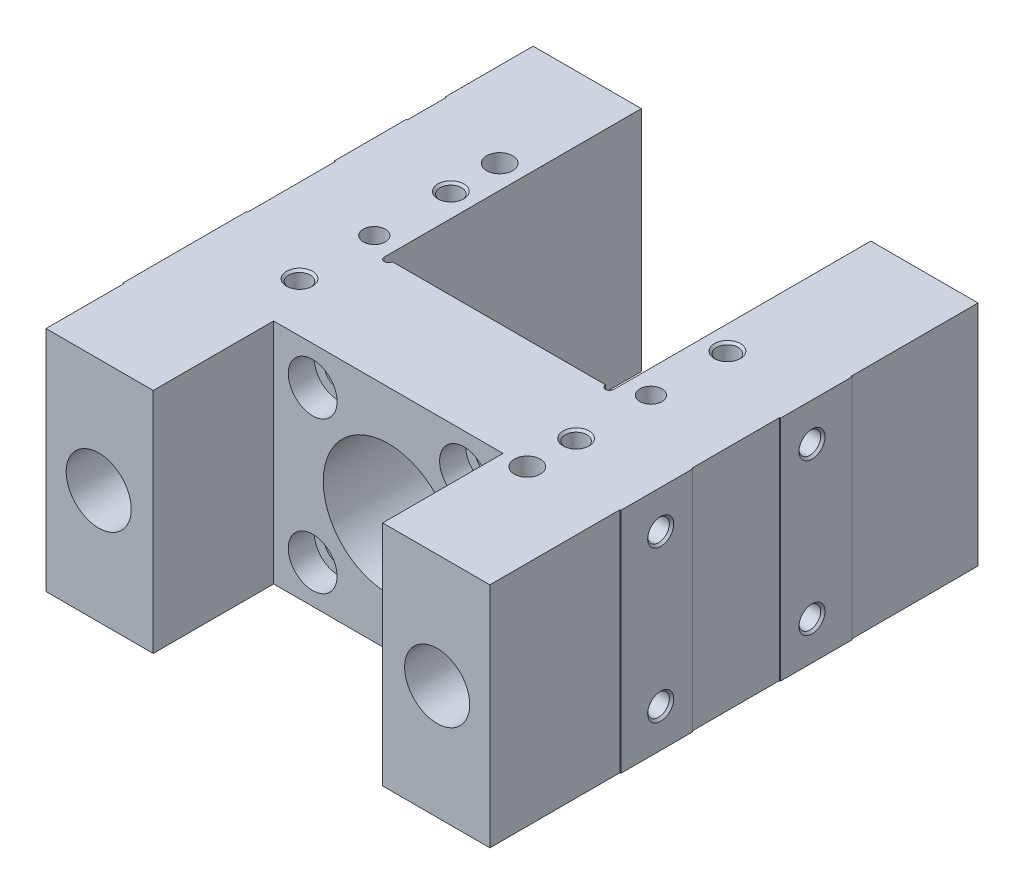
SolidWorks part; units mm, degrees
ref_plane "Front Plane" through (0, 0, 0) normal (0, 0, 1) x (1, 0, 0)
ref_plane "Top Plane" through (0, 0, 0) normal (0, 1, 0) x (1, 0, 0)
ref_plane "Right Plane" through (0, 0, 0) normal (1, 0, 0) x (0, 0, -1)
sketch "Sketch1" plane through (0, 0, 0) normal (0, 1, 0) x (1, 0, 0)
  line L0 (-68.5, -71) -> (-35.25, -71)
  line L1 (-35.25, -71) -> (-35.25, -34)
  line L2 (-35.25, -34) -> (35.25, -34)
  line L3 (35.25, -34) -> (35.25, -71)
  line L4 (35.25, -71) -> (68.5, -71)
  line L5 (68.5, -71) -> (68.5, 79)
  line L6 (68.5, 79) -> (35.25, 79)
  line L7 (35.25, 79) -> (35.25, 0)
  line L8 (32.75, 0) -> (-32.75, 0)
  line L9 (-35.25, 0) -> (-35.25, 79)
  line L10 (-35.25, 79) -> (-68.5, 79)
  line L11 (-68.5, 79) -> (-68.5, -71)
  arc A0 (35.25, 0) -> (32.75, 0) centre (34, 0) cw
  arc A1 (-32.75, 0) -> (-35.25, 0) centre (-34, 0) cw
extrude "Boss-Extrude1" add sketch "Sketch1" against normal blind 35 and the other way blind 35
sketch "Sketch2" plane through (0, 0, 0) normal (1, 0, 0) x (0, 0, -1)
  line L0 (-35, 0) -> (-35, 20)
  line L1 (-35, 20) -> (1, 20)
  line L2 (1, 20) -> (1, 0)
  line L3 (1, 0) -> (-35, 0)
  line L4 (1, 0) -> (-35, 0) construction
revolve "Cut-Revolve1" cut sketch "Sketch2" angle 360 about L4 reverse direction yes
ref_plane "Plane1" through (-23.25, 0, 0) normal (1, 0, 0) x (0, 0, -1)
sketch "Sketch3" plane through (-23.25, 0, 0) normal (1, 0, 0) x (0, 0, -1)
  line L0 (-34, 23.25) -> (-34, 30.75)
  line L1 (-34, 30.75) -> (-26, 30.75)
  line L2 (-26, 30.75) -> (-26, 27.75)
  line L3 (-26, 27.75) -> (0, 27.75)
  line L4 (0, 27.75) -> (0, 23.25)
  line L5 (0, 23.25) -> (-34, 23.25)
  line L6 (0, 23.25) -> (-34, 23.25) construction
revolve "Cut-Revolve2" cut sketch "Sketch3" angle 360 about L6 reverse direction yes
sketch "Sketch4" plane through (-23.25, 0, 0) normal (1, 0, 0) x (0, 0, -1)
  line L0 (-34, -23.25) -> (-34, -15.75)
  line L1 (-34, -15.75) -> (-26, -15.75)
  line L2 (-26, -15.75) -> (-26, -18.75)
  line L3 (-26, -18.75) -> (0, -18.75)
  line L4 (0, -18.75) -> (0, -23.25)
  line L5 (0, -23.25) -> (-34, -23.25)
  line L6 (0, -23.25) -> (-34, -23.25) construction
revolve "Cut-Revolve3" cut sketch "Sketch4" angle 360 about L6 reverse direction yes
ref_plane "Plane2" through (23.25, 0, 0) normal (1, 0, 0) x (0, 0, -1)
sketch "Sketch5" plane through (23.25, 0, 0) normal (1, 0, 0) x (0, 0, -1)
  line L0 (-34, 23.25) -> (-34, 30.75)
  line L1 (-34, 30.75) -> (-26, 30.75)
  line L2 (-26, 30.75) -> (-26, 27.75)
  line L3 (-26, 27.75) -> (0, 27.75)
  line L4 (0, 27.75) -> (0, 23.25)
  line L5 (0, 23.25) -> (-34, 23.25)
  line L6 (0, 23.25) -> (-34, 23.25) construction
revolve "Cut-Revolve4" cut sketch "Sketch5" angle 360 about L6 reverse direction yes
sketch "Sketch6" plane through (23.25, 0, 0) normal (1, 0, 0) x (0, 0, -1)
  line L0 (-34, -23.25) -> (-34, -15.75)
  line L1 (-34, -15.75) -> (-26, -15.75)
  line L2 (-26, -15.75) -> (-26, -18.75)
  line L3 (-26, -18.75) -> (0, -18.75)
  line L4 (0, -18.75) -> (0, -23.25)
  line L5 (0, -23.25) -> (-34, -23.25)
  line L6 (0, -23.25) -> (-34, -23.25) construction
revolve "Cut-Revolve5" cut sketch "Sketch6" angle 360 about L6 reverse direction yes
ref_plane "Plane3" through (0, 0, 18.8) normal (0, 0, 1) x (1, 0, 0)
hole_wizard "Hole1" positions "Sketch8" profile "Sketch7" legacy
sketch "Sketch8" plane through (0, 35, 0) normal (0, 1, 0) x (1, 0, 0)
  point P0 (42.5, -18.8)
sketch "Sketch7" plane through (42.5, 35, 18.8) normal (1, 0, 0) x (0, 0, 1)
  line L0 (0, 0) -> (0, 21.3333)
  line L1 (0, 21.3333) -> (3.3235, 19.4145)
  line L2 (3.3235, 19.4145) -> (3.3235, 0.6765)
  line L3 (3.3235, 0.6765) -> (4, 0)
  line L4 (4, 0) -> (0, 0)
  line L5 (0, -14.3089) -> (0, 102.4216) construction
  line L6 (0, 21.3333) -> (-3.3235, 19.4145) construction
  line L7 (-3.3235, 0.6765) -> (-4, 0) construction
  dimension "Diameter" = 6.647
  dimension "Depth" = 19.4145
  dimension "C-Sink Diameter" = 8
  dimension "C-Sink Angle" = 90
  dimension "Drill Angle" = 120
cosmetic thread "Cosmetic Thread1" parameters "D1"=16, "D2"=8
hole_wizard "Hole2" positions "Sketch10" profile "Sketch9" legacy
sketch "Sketch10" plane through (0, 35, 0) normal (0, 1, 0) x (1, 0, 0)
  point P0 (-42.5, -18.8)
sketch "Sketch9" plane through (-42.5, 35, 18.8) normal (1, 0, 0) x (0, 0, 1)
  line L0 (0, 0) -> (0, 21.3333)
  line L1 (0, 21.3333) -> (3.3235, 19.4145)
  line L2 (3.3235, 19.4145) -> (3.3235, 0.6765)
  line L3 (3.3235, 0.6765) -> (4, 0)
  line L4 (4, 0) -> (0, 0)
  line L5 (0, -14.3089) -> (0, 102.4216) construction
  line L6 (0, 21.3333) -> (-3.3235, 19.4145) construction
  line L7 (-3.3235, 0.6765) -> (-4, 0) construction
  dimension "Diameter" = 6.647
  dimension "Depth" = 19.4145
  dimension "C-Sink Diameter" = 8
  dimension "C-Sink Angle" = 90
  dimension "Drill Angle" = 120
cosmetic thread "Cosmetic Thread2" parameters "D1"=16, "D2"=8
sketch "Sketch11" plane through (0, 0, 18.8) normal (0, 0, 1) x (1, 0, 0)
  line L0 (48.5, 23.25) -> (50.4188, 26.5735)
  line L1 (50.4188, 26.5735) -> (67.8235, 26.5735)
  line L2 (67.8235, 26.5735) -> (68.5, 27.25)
  line L3 (68.5, 27.25) -> (68.5, 23.25)
  line L4 (68.5, 23.25) -> (48.5, 23.25)
  line L5 (68.5, 23.25) -> (48.5, 23.25) construction
revolve "Cut-Revolve6" cut sketch "Sketch11" angle 360 about L5
cosmetic thread "Cosmetic Thread3" parameters "D1"=16, "D2"=8
sketch "Sketch12" plane through (0, 0, 18.8) normal (0, 0, 1) x (1, 0, 0)
  line L0 (48.5, -23.25) -> (50.4188, -19.9265)
  line L1 (50.4188, -19.9265) -> (67.8235, -19.9265)
  line L2 (67.8235, -19.9265) -> (68.5, -19.25)
  line L3 (68.5, -19.25) -> (68.5, -23.25)
  line L4 (68.5, -23.25) -> (48.5, -23.25)
  line L5 (68.5, -23.25) -> (48.5, -23.25) construction
revolve "Cut-Revolve7" cut sketch "Sketch12" angle 360 about L5
cosmetic thread "Cosmetic Thread4" parameters "D1"=16, "D2"=8
sketch "Sketch13" plane through (0, 0, 18.8) normal (0, 0, 1) x (1, 0, 0)
  line L0 (-68.5, 23.25) -> (-68.5, 27.25)
  line L1 (-68.5, 27.25) -> (-67.8235, 26.5735)
  line L2 (-67.8235, 26.5735) -> (-50.4188, 26.5735)
  line L3 (-50.4188, 26.5735) -> (-48.5, 23.25)
  line L4 (-48.5, 23.25) -> (-68.5, 23.25)
  line L5 (-48.5, 23.25) -> (-68.5, 23.25) construction
revolve "Cut-Revolve8" cut sketch "Sketch13" angle 360 about L5
cosmetic thread "Cosmetic Thread5" parameters "D1"=16, "D2"=8
sketch "Sketch14" plane through (0, 0, 18.8) normal (0, 0, 1) x (1, 0, 0)
  line L0 (-68.5, -23.25) -> (-68.5, -19.25)
  line L1 (-68.5, -19.25) -> (-67.8235, -19.9265)
  line L2 (-67.8235, -19.9265) -> (-50.4188, -19.9265)
  line L3 (-50.4188, -19.9265) -> (-48.5, -23.25)
  line L4 (-48.5, -23.25) -> (-68.5, -23.25)
  line L5 (-48.5, -23.25) -> (-68.5, -23.25) construction
revolve "Cut-Revolve9" cut sketch "Sketch14" angle 360 about L5 reverse direction yes
cosmetic thread "Cosmetic Thread6" parameters "D1"=16, "D2"=8
ref_plane "Plane4" through (0, 0, -27.7) normal (0, 0, 1) x (1, 0, 0)
hole_wizard "Hole3" positions "Sketch16" profile "Sketch15" legacy
sketch "Sketch16" plane through (0, 35, 0) normal (0, 1, 0) x (1, 0, 0)
  point P0 (42.5, 27.7)
sketch "Sketch15" plane through (42.5, 35, -27.7) normal (1, 0, 0) x (0, 0, 1)
  line L0 (0, 0) -> (0, 21.3333)
  line L1 (0, 21.3333) -> (3.3235, 19.4145)
  line L2 (3.3235, 19.4145) -> (3.3235, 0.6765)
  line L3 (3.3235, 0.6765) -> (4, 0)
  line L4 (4, 0) -> (0, 0)
  line L5 (0, -14.3089) -> (0, 102.4216) construction
  line L6 (0, 21.3333) -> (-3.3235, 19.4145) construction
  line L7 (-3.3235, 0.6765) -> (-4, 0) construction
  dimension "Diameter" = 6.647
  dimension "Depth" = 19.4145
  dimension "C-Sink Diameter" = 8
  dimension "C-Sink Angle" = 90
  dimension "Drill Angle" = 120
cosmetic thread "Cosmetic Thread7" parameters "D1"=16, "D2"=8
sketch "Sketch17" plane through (0, 0, -27.7) normal (0, 0, 1) x (1, 0, 0)
  line L0 (-42.5, 35) -> (-38.5, 35)
  line L1 (-38.5, 35) -> (-39.1765, 34.3235)
  line L2 (-39.1765, 34.3235) -> (-39.1765, 15.5855)
  line L3 (-39.1765, 15.5855) -> (-42.5, 13.6667)
  line L4 (-42.5, 13.6667) -> (-42.5, 35)
  line L5 (-42.5, 13.6667) -> (-42.5, 35) construction
revolve "Cut-Revolve10" cut sketch "Sketch17" angle 360 about L5
cosmetic thread "Cosmetic Thread8" parameters "D1"=16, "D2"=8
sketch "Sketch18" plane through (0, 0, -27.7) normal (0, 0, 1) x (1, 0, 0)
  line L0 (48.5, 23.25) -> (50.4188, 26.5735)
  line L1 (50.4188, 26.5735) -> (67.8235, 26.5735)
  line L2 (67.8235, 26.5735) -> (68.5, 27.25)
  line L3 (68.5, 27.25) -> (68.5, 23.25)
  line L4 (68.5, 23.25) -> (48.5, 23.25)
  line L5 (68.5, 23.25) -> (48.5, 23.25) construction
revolve "Cut-Revolve11" cut sketch "Sketch18" angle 360 about L5
cosmetic thread "Cosmetic Thread9" parameters "D1"=16, "D2"=8
sketch "Sketch19" plane through (0, 0, -27.7) normal (0, 0, 1) x (1, 0, 0)
  line L0 (48.5, -23.25) -> (50.4188, -19.9265)
  line L1 (50.4188, -19.9265) -> (67.8235, -19.9265)
  line L2 (67.8235, -19.9265) -> (68.5, -19.25)
  line L3 (68.5, -19.25) -> (68.5, -23.25)
  line L4 (68.5, -23.25) -> (48.5, -23.25)
  line L5 (68.5, -23.25) -> (48.5, -23.25) construction
revolve "Cut-Revolve12" cut sketch "Sketch19" angle 360 about L5
cosmetic thread "Cosmetic Thread10" parameters "D1"=16, "D2"=8
sketch "Sketch20" plane through (0, 0, -27.7) normal (0, 0, 1) x (1, 0, 0)
  line L0 (-68.5, 23.25) -> (-68.5, 27.25)
  line L1 (-68.5, 27.25) -> (-67.8235, 26.5735)
  line L2 (-67.8235, 26.5735) -> (-50.4188, 26.5735)
  line L3 (-50.4188, 26.5735) -> (-48.5, 23.25)
  line L4 (-48.5, 23.25) -> (-68.5, 23.25)
  line L5 (-48.5, 23.25) -> (-68.5, 23.25) construction
revolve "Cut-Revolve13" cut sketch "Sketch20" angle 360 about L5
cosmetic thread "Cosmetic Thread11" parameters "D1"=16, "D2"=8
sketch "Sketch21" plane through (0, 0, -27.7) normal (0, 0, 1) x (1, 0, 0)
  line L0 (-68.5, -23.25) -> (-68.5, -19.25)
  line L1 (-68.5, -19.25) -> (-67.8235, -19.9265)
  line L2 (-67.8235, -19.9265) -> (-50.4188, -19.9265)
  line L3 (-50.4188, -19.9265) -> (-48.5, -23.25)
  line L4 (-48.5, -23.25) -> (-68.5, -23.25)
  line L5 (-48.5, -23.25) -> (-68.5, -23.25) construction
revolve "Cut-Revolve14" cut sketch "Sketch21" angle 360 about L5
cosmetic thread "Cosmetic Thread12" parameters "D1"=16, "D2"=8
ref_plane "Plane5" through (0, 0, -63) normal (0, 0, 1) x (1, 0, 0)
sketch "Sketch22" plane through (0, 0, -63) normal (0, 0, 1) x (1, 0, 0)
  line L0 (-68.5, 23.25) -> (-68.5, 27.25)
  line L1 (-68.5, 27.25) -> (-67.8235, 26.5735)
  line L2 (-67.8235, 26.5735) -> (-50.4188, 26.5735)
  line L3 (-50.4188, 26.5735) -> (-48.5, 23.25)
  line L4 (-48.5, 23.25) -> (-68.5, 23.25)
  line L5 (-48.5, 23.25) -> (-68.5, 23.25) construction
revolve "Cut-Revolve15" cut sketch "Sketch22" angle 360 about L5
cosmetic thread "Cosmetic Thread13" parameters "D1"=16, "D2"=8
sketch "Sketch23" plane through (0, 0, -63) normal (0, 0, 1) x (1, 0, 0)
  line L0 (-68.5, -23.25) -> (-68.5, -19.25)
  line L1 (-68.5, -19.25) -> (-67.8235, -19.9265)
  line L2 (-67.8235, -19.9265) -> (-50.4188, -19.9265)
  line L3 (-50.4188, -19.9265) -> (-48.5, -23.25)
  line L4 (-48.5, -23.25) -> (-68.5, -23.25)
  line L5 (-48.5, -23.25) -> (-68.5, -23.25) construction
revolve "Cut-Revolve16" cut sketch "Sketch23" angle 360 about L5
cosmetic thread "Cosmetic Thread14" parameters "D1"=16, "D2"=8
ref_plane "Plane6" through (0, 0, 37) normal (0, 0, 1) x (1, 0, 0)
sketch "Sketch24" plane through (0, 0, 37) normal (0, 0, 1) x (1, 0, 0)
  line L0 (-68.5, 23.25) -> (-68.5, 27.25)
  line L1 (-68.5, 27.25) -> (-67.8235, 26.5735)
  line L2 (-67.8235, 26.5735) -> (-50.4188, 26.5735)
  line L3 (-50.4188, 26.5735) -> (-48.5, 23.25)
  line L4 (-48.5, 23.25) -> (-68.5, 23.25)
  line L5 (-48.5, 23.25) -> (-68.5, 23.25) construction
revolve "Cut-Revolve17" cut sketch "Sketch24" angle 360 about L5
cosmetic thread "Cosmetic Thread15" parameters "D1"=16, "D2"=8
sketch "Sketch25" plane through (0, 0, 37) normal (0, 0, 1) x (1, 0, 0)
  line L0 (-68.5, -23.25) -> (-68.5, -19.25)
  line L1 (-68.5, -19.25) -> (-67.8235, -19.9265)
  line L2 (-67.8235, -19.9265) -> (-50.4188, -19.9265)
  line L3 (-50.4188, -19.9265) -> (-48.5, -23.25)
  line L4 (-48.5, -23.25) -> (-68.5, -23.25)
  line L5 (-48.5, -23.25) -> (-68.5, -23.25) construction
revolve "Cut-Revolve18" cut sketch "Sketch25" angle 360 about L5
cosmetic thread "Cosmetic Thread16" parameters "D1"=16, "D2"=8
ref_plane "Plane7" through (0, 0, -79) normal (0, 0, 1) x (1, 0, 0)
sketch "Sketch26" plane through (0, 0, -79) normal (0, 0, 1) x (1, 0, 0)
  circle A0 centre (52, 0) radius 10
extrude "Cut-Extrude1" cut sketch "Sketch26" along normal blind 150
sketch "Sketch27" plane through (0, 0, -79) normal (0, 0, 1) x (1, 0, 0)
  circle A0 centre (-52, 0) radius 10
extrude "Cut-Extrude2" cut sketch "Sketch27" along normal blind 150
ref_plane "Plane8" through (0, 0, 26) normal (0, 0, 1) x (1, 0, 0)
ref_plane "Plane9" through (0, 0, 0) normal (0, 0, 1) x (1, 0, 0)
sketch "Sketch28" plane through (0, 0, 0) normal (0, 1, 0) x (1, 0, 0)
  line L0 (-88.5, -91) -> (88.5, -91)
  line L1 (88.5, -91) -> (88.5, 99)
  line L2 (88.5, 99) -> (-88.5, 99)
  line L3 (-88.5, 99) -> (-88.5, -91)
  line L4 (-68.5, 18) -> (-68.2, 18)
  line L5 (-68.2, 18) -> (-68.2, -9)
  line L6 (-68.2, -9) -> (-68.5, -9)
  line L7 (-68.5, -9) -> (-68.5, -47)
  line L8 (-68.5, -47) -> (-68.2, -47)
  line L9 (-68.2, -47) -> (-68.2, -71)
  line L10 (-68.2, -71) -> (68.2, -71)
  line L11 (68.2, -71) -> (68.2, -31)
  line L12 (68.2, -31) -> (68.5, -31)
  line L13 (68.5, -31) -> (68.5, -9)
  line L14 (68.5, -9) -> (68.2, -9)
  line L15 (68.2, -9) -> (68.2, 18)
  line L16 (68.2, 18) -> (68.5, 18)
  line L17 (68.5, 18) -> (68.5, 40)
  line L18 (68.5, 40) -> (68.2, 40)
  line L19 (68.2, 40) -> (68.2, 79)
  line L20 (68.2, 79) -> (-68.5, 79)
  line L21 (-68.5, 79) -> (-68.5, 52)
  line L22 (-68.5, 52) -> (-68.2, 52)
  line L23 (-68.2, 52) -> (-68.2, 40)
  line L24 (-68.2, 40) -> (-68.5, 40)
  line L25 (-68.5, 40) -> (-68.5, 18)
extrude "Cut-Extrude3" cut sketch "Sketch28" along normal blind 70 and the other way blind 70
ref_plane "Plane10" through (0, 0, 18.8) normal (0, 0, 1) x (1, 0, 0)
ref_plane "Plane11" through (-68.2, 0, 0) normal (1, 0, 0) x (0, 0, -1)
ref_plane "Plane12" through (0, 35, 0) normal (0, 1, 0) x (1, 0, 0)
ref_plane "DIN912 1 XY" through (0, 0, 26) normal (0, 0, 1) x (1, 0, 0)
ref_plane "DIN912 1 XZ" through (0, 23.25, 0) normal (0, -1, 0) x (-1, 0, 0)
ref_plane "DIN912 1 YZ" through (23.25, 0, 0) normal (1, 0, 0) x (0, 0, -1)
ref_axis "DIN912 1 X" through (-80.9, 23.25, 26) along (1, 0, 0)
ref_axis "DIN912 1 Y" through (23.25, -50, 26) along (0, 1, 0)
ref_axis "DIN912 1 Z" through (23.25, 23.25, 80.9) along (0, 0, -1)
sketch3d "DIN912 1"
  point P0 (23.25, 23.25, 26)
ref_plane "DIN912 2 XY" through (0, 0, 26) normal (0, 0, 1) x (1, 0, 0)
ref_plane "DIN912 2 XZ" through (0, 23.25, 0) normal (0, -1, 0) x (-1, 0, 0)
ref_plane "DIN912 2 YZ" through (-23.25, 0, 0) normal (1, 0, 0) x (0, 0, -1)
ref_axis "DIN912 2 X" through (-80.9, 23.25, 26) along (1, 0, 0)
ref_axis "DIN912 2 Y" through (-23.25, -50, 26) along (0, 1, 0)
ref_axis "DIN912 2 Z" through (-23.25, 23.25, 80.9) along (0, 0, -1)
sketch3d "DIN912 2"
  point P0 (-23.25, 23.25, 26)
ref_plane "DIN912 3 XY" through (0, 0, 26) normal (0, 0, 1) x (1, 0, 0)
ref_plane "DIN912 3 XZ" through (0, -23.25, 0) normal (0, -1, 0) x (-1, 0, 0)
ref_plane "DIN912 3 YZ" through (23.25, 0, 0) normal (1, 0, 0) x (0, 0, -1)
ref_axis "DIN912 3 X" through (-80.9, -23.25, 26) along (1, 0, 0)
ref_axis "DIN912 3 Y" through (23.25, -50, 26) along (0, 1, 0)
ref_axis "DIN912 3 Z" through (23.25, -23.25, 80.9) along (0, 0, -1)
sketch3d "DIN912 3"
  point P0 (23.25, -23.25, 26)
ref_plane "DIN912 4 XY" through (0, 0, 26) normal (0, 0, 1) x (1, 0, 0)
ref_plane "DIN912 4 XZ" through (0, -23.25, 0) normal (0, -1, 0) x (-1, 0, 0)
ref_plane "DIN912 4 YZ" through (-23.25, 0, 0) normal (1, 0, 0) x (0, 0, -1)
ref_axis "DIN912 4 X" through (-80.9, -23.25, 26) along (1, 0, 0)
ref_axis "DIN912 4 Y" through (-23.25, -50, 26) along (0, 1, 0)
ref_axis "DIN912 4 Z" through (-23.25, -23.25, 80.9) along (0, 0, -1)
sketch3d "DIN912 4"
  point P0 (-23.25, -23.25, 26)
ref_plane "JOCH XY" through (0, 0, 0) normal (0, 0, 1) x (1, 0, 0)
ref_plane "JOCH XZ" through (0, 0, 0) normal (0, -1, 0) x (-1, 0, 0)
ref_plane "JOCH YZ" through (0, 0, 0) normal (1, 0, 0) x (0, 0, -1)
ref_axis "JOCH X" through (-80.9, 0, 0) along (1, 0, 0)
ref_axis "JOCH Y" through (0, -50, 0) along (0, 1, 0)
ref_axis "JOCH Z" through (0, 0, 80.9) along (0, 0, -1)
sketch3d "JOCH"
  point P0 (0, 0, 0)
ref_plane "SCHRAUBE1 XY" through (0, 0, 26) normal (0, 0, 1) x (1, 0, 0)
ref_plane "SCHRAUBE1 XZ" through (0, 23.25, 0) normal (0, -1, 0) x (-1, 0, 0)
ref_plane "SCHRAUBE1 YZ" through (23.25, 0, 0) normal (1, 0, 0) x (0, 0, -1)
ref_axis "SCHRAUBE1 X" through (-80.9, 23.25, 26) along (1, 0, 0)
ref_axis "SCHRAUBE1 Y" through (23.25, -50, 26) along (0, 1, 0)
ref_axis "SCHRAUBE1 Z" through (23.25, 23.25, 80.9) along (0, 0, -1)
sketch3d "SCHRAUBE1"
  point P0 (23.25, 23.25, 26)
ref_plane "SCHRAUBE2 XY" through (0, 0, 26) normal (0, 0, 1) x (1, 0, 0)
ref_plane "SCHRAUBE2 XZ" through (0, 23.25, 0) normal (0, -1, 0) x (-1, 0, 0)
ref_plane "SCHRAUBE2 YZ" through (-23.25, 0, 0) normal (1, 0, 0) x (0, 0, -1)
ref_axis "SCHRAUBE2 X" through (-80.9, 23.25, 26) along (1, 0, 0)
ref_axis "SCHRAUBE2 Y" through (-23.25, -50, 26) along (0, 1, 0)
ref_axis "SCHRAUBE2 Z" through (-23.25, 23.25, 80.9) along (0, 0, -1)
sketch3d "SCHRAUBE2"
  point P0 (-23.25, 23.25, 26)
ref_plane "SCHRAUBE3 XY" through (0, 0, 26) normal (0, 0, 1) x (1, 0, 0)
ref_plane "SCHRAUBE3 XZ" through (0, -23.25, 0) normal (0, -1, 0) x (-1, 0, 0)
ref_plane "SCHRAUBE3 YZ" through (-23.25, 0, 0) normal (1, 0, 0) x (0, 0, -1)
ref_axis "SCHRAUBE3 X" through (-80.9, -23.25, 26) along (1, 0, 0)
ref_axis "SCHRAUBE3 Y" through (-23.25, -50, 26) along (0, 1, 0)
ref_axis "SCHRAUBE3 Z" through (-23.25, -23.25, 80.9) along (0, 0, -1)
sketch3d "SCHRAUBE3"
  point P0 (-23.25, -23.25, 26)
ref_plane "SCHRAUBE4 XY" through (0, 0, 26) normal (0, 0, 1) x (1, 0, 0)
ref_plane "SCHRAUBE4 XZ" through (0, -23.25, 0) normal (0, -1, 0) x (-1, 0, 0)
ref_plane "SCHRAUBE4 YZ" through (23.25, 0, 0) normal (1, 0, 0) x (0, 0, -1)
ref_axis "SCHRAUBE4 X" through (-80.9, -23.25, 26) along (1, 0, 0)
ref_axis "SCHRAUBE4 Y" through (23.25, -50, 26) along (0, 1, 0)
ref_axis "SCHRAUBE4 Z" through (23.25, -23.25, 80.9) along (0, 0, -1)
sketch3d "SCHRAUBE4"
  point P0 (23.25, -23.25, 26)
ref_plane "ZYLINDER XY" through (0, 0, 0) normal (0, 0, 1) x (1, 0, 0)
ref_plane "ZYLINDER XZ" through (0, 0, 0) normal (0, -1, 0) x (-1, 0, 0)
ref_plane "ZYLINDER YZ" through (0, 0, 0) normal (1, 0, 0) x (0, 0, -1)
ref_axis "ZYLINDER X" through (-80.9, 0, 0) along (1, 0, 0)
ref_axis "ZYLINDER Y" through (0, -50, 0) along (0, 1, 0)
ref_axis "ZYLINDER Z" through (0, 0, 80.9) along (0, 0, -1)
sketch3d "ZYLINDER"
  point P0 (0, 0, 0)
other "Freeze***"
sketch "Sketch29" plane through (0, 35, 0) normal (0, 1, 0) x (1, 0, 0)
  circle A0 centre (-42.5, 42.7) radius 4
  circle A1 centre (42.5, -33.8) radius 4
  dimension "D1" = 8
  dimension "D2" = 15
  dimension "D3" = 15
extrude "Cut-Extrude4" cut sketch "Sketch29" against normal blind 17.5
sketch "Sketch30" plane through (0, 35, 0) normal (0, 1, 0) x (1, 0, 0)
  point P0 (-42.5, 4.2)
  point P1 (42.5, 4.2)
  dimension "D1" = 23
hole_wizard "M8 Tapped Hole1" positions "Sketch31" profile "Sketch32" tap size "M8" standard "ISO"
sketch "Sketch31" plane through (0, 35, 0) normal (0, 1, 0) x (1, 0, 0)
  point P0 (-42.5, 4.2)
  point P3 (42.5, 4.2)
sketch "Sketch32" plane through (-42.5, 35, -4.2) normal (1, 0, 0) x (0, 0, 1)
  line L0 (0, 0) -> (0, 21.7929)
  line L1 (0, 21.7929) -> (3.4, 19.75)
  line L2 (3.4, 19.75) -> (3.4, 0)
  line L5 (3.4, 0) -> (0, 0)
  line L10 (0, 21.7929) -> (-3.4, 19.75) construction
  line L11 (0, -6.35) -> (0, 107.95) construction
  dimension "Tap Drill Dia." = 6.8
  dimension "Tap Drill Depth" = 19.75
  dimension "Drill Angle" = 118
cosmetic thread "Hole Thread1" parameters "D1"=16, "D2"=8
cosmetic thread "Hole Thread2" parameters "D1"=16, "D2"=8
